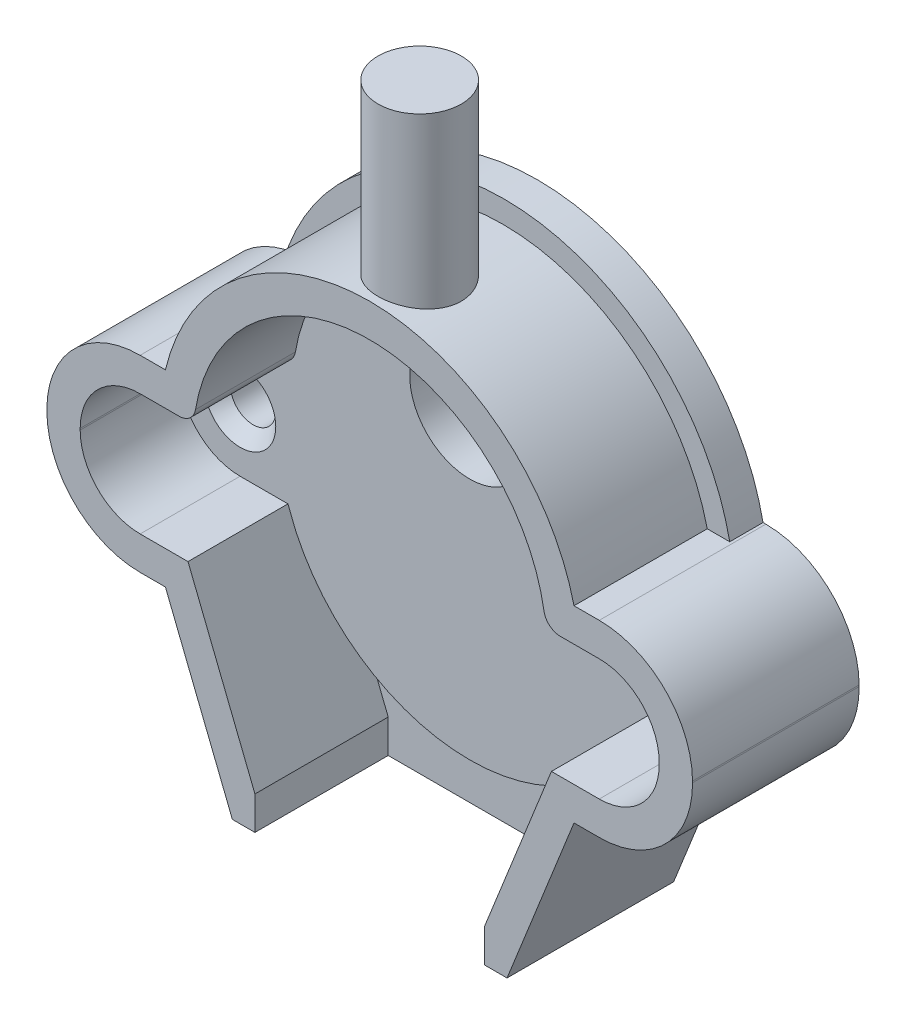
SolidWorks part; units mm, degrees
other "Markup1"
sketch "Sketch20" plane through (-24.612, 32.1867, 12.7) normal (-0.5124, 0.2446, 0.8232) x (0.0203, 0.9618, -0.2731)
other "Markup2"
sketch "Sketch21" plane through (-24.612, 32.1867, 12.7) normal (-0.5124, 0.2446, 0.8232) x (0.0203, 0.9618, -0.2731)
ref_plane "Front Plane" through (0, 0, 0) normal (0, 0, 1) x (1, 0, 0)
ref_plane "Top Plane" through (0, 0, 0) normal (0, 1, 0) x (1, 0, 0)
ref_plane "Right Plane" through (0, 0, 0) normal (1, 0, 0) x (0, 0, -1)
sketch "Sketch1" plane through (0, 0, 0) normal (0, 0, 1) x (1, 0, 0)
  line L0 (10.16, 0) -> (13.9, 0) construction
  line L1 (13.9, 0) -> (10.16, 0) construction
  line L2 (-17.5, 0.0566) -> (-17.5, -0.0566) construction
  line L3 (17.5, 7.1686) -> (15.5744, 7.1686)
  line L4 (17.5, -7.1686) -> (15.5744, -7.1686)
  line L5 (-24.612, 0.0566) -> (-24.612, -0.0566)
  line L6 (24.6118, 0.1131) -> (24.6118, 0)
  line L7 (-15.5744, 7.1686) -> (-17.5, 7.1686)
  line L8 (-15.5744, -7.1686) -> (-17.5, -7.1686)
  line L11 (-10.4702, -19.9603) -> (10.4702, -19.9603)
  line L13 (17.5, 0.0566) -> (17.5, -0.0566) construction
  line L14 (-17.5, 0) -> (17.5, 0) construction
  line L15 (55, 0) -> (-55, 0) construction
  line L16 (-10.4702, -19.9603) -> (-15.5744, -7.1686)
  line L17 (10.4702, -19.9603) -> (15.5744, -7.1686)
  arc A1 (-17.5, -7.1686) -> (-24.612, -0.0566) centre (-17.5, -0.0566) cw
  arc A2 (-17.5, 7.1686) -> (-24.612, 0.0566) centre (-17.5, 0.0566) ccw
  arc A5 (17.5, -7.1686) -> (24.6118, 0) centre (17.5, -0.0566) ccw
  arc A6 (17.5, 7.1686) -> (24.6118, 0.1131) centre (17.5, 0.0566) cw
  arc A9 (15.5744, 7.1686) -> (-15.5744, 7.1686) centre (0, 3.4819) ccw
  point P20 (0, -3.4819)
  point P25 (0, 3.4819)
  point P26 (0, 0)
  point P30 (0, 0)
  dimension "D1" = 1.9256
  dimension "D2" = 0.1131
  dimension "D3" = 35
  dimension "D4" = 7.112
  dimension "D5" = 1.9256
  dimension "D7" = 20.9405
extrude "Boss-Extrude1" add sketch "Sketch1" along normal blind 12.7
sketch "Sketch22" plane through (0, 0, 0) normal (0, 0, -1) x (-1, 0, 0)
  line L0 (-17.2875, 7.1686) -> (17.1369, 7.1686)
  arc A0 (17.1369, 7.1686) -> (-17.2875, 7.1686) centre (-0.0753, 3.628) ccw
shell "Shell1" thickness 2.54 removed face at (0, -1.9647, 12.7)
extrude "Boss-Extrude7" add sketch "Sketch22" against normal blind 2.54
sketch "Sketch7" plane through (0, -17.4203, 0) normal (0, 1, 0) x (1, 0, 0)
  line L1 (-8.749, -12.7) -> (8.749, -12.7)
  line L2 (-8.749, -12.7) -> (-8.749, -2.54)
  line L3 (-8.749, -2.54) -> (8.749, -2.54)
  line L4 (8.749, -12.7) -> (8.749, -2.54)
extrude "Cut-Extrude5" cut sketch "Sketch7" against normal through all
sketch "Sketch13" plane through (0, 0, 2.54) normal (0, 0, 1) x (1, 0, 0)
  line L1 (-17.5, -4.6286) -> (-13.8522, -4.6286)
  line L3 (-16.51, 4.6286) -> (-13.4159, 4.6286)
  line L5 (13.8522, -4.6286) -> (16.51, -4.6286)
  line L6 (13.4159, 4.6286) -> (17.5, 4.6286)
  line L8 (0, 0) -> (0, 8.509) construction
  arc A1 (-16.51, 4.6286) -> (-19.1193, -4.3322) centre (-17.5, 0.0566) ccw
  arc A2 (-19.1193, -4.3322) -> (-17.5, -4.6286) centre (-17.5, -0.0566) ccw
  arc A3 (19.1193, 4.3322) -> (17.5, 4.6286) centre (17.5, 0.0566) ccw
  arc A4 (16.51, -4.6286) -> (19.1193, 4.3322) centre (17.5, -0.0566) ccw
  arc A6 (-13.8522, -4.6286) -> (13.8522, -4.6286) centre (0, 0) ccw
  circle A7 centre (0, 8.509) radius 4.572
  arc A8 (13.4159, 4.6286) -> (-13.4159, 4.6286) centre (0, 3.4819) ccw
  dimension "D2" = 9.144
  dimension "D1" = 8.509
extrude "Boss-Extrude3" add sketch "Sketch13" along normal blind 2.54
sketch "Sketch14" plane through (0, 0, 5.08) normal (0, 0, 1) x (1, 0, 0)
  line L0 (0, 0) -> (0, 8.5) construction
  line L1 (-17.5, 0) -> (17.5, 0) construction
  circle A0 centre (0, 8.5) radius 2.667
  point P6 (0, 0)
  dimension "D1" = 35
  dimension "D2" = 8.5
extrude "Cut-Extrude7" cut sketch "Sketch14" against normal through all both and the other way through all
hole_wizard "#8-32 Tapped Hole1" positions "Sketch16" profile "Sketch17" tap size "#8-32" standard "ANSI Inch" end condition through all
sketch "Sketch16" plane through (0, 0, 5.08) normal (0, 0, 1) x (1, 0, 0)
  point P0 (-17.5, 0)
  point P3 (17.5, 0)
sketch "Sketch17" plane through (-17.5, 0, 5.08) normal (1, 0, 0) x (0, -1, 0)
  line L0 (0, 0) -> (0, 5.08)
  line L1 (0, 5.08) -> (1.7272, 5.08)
  line L2 (1.7272, 5.08) -> (1.7272, 0.9906)
  line L3 (1.7272, 0.9906) -> (2.7178, 0)
  line L5 (2.7178, 0) -> (0, 0)
  line L6 (-1.7272, 0.9906) -> (-2.7178, 0) construction
  line L11 (0, -6.35) -> (0, 107.95) construction
  dimension "Thru Tap Drill Dia." = 3.4544
  dimension "Thru Tap Drill Depth" = 5.08
  dimension "Near C'Sink Dia." = 5.4356
  dimension "Near C'Sink Angle" = 90
cosmetic thread "Hole Thread1" parameters "D2"=4.1656
cosmetic thread "Hole Thread2" parameters "D2"=4.1656
ref_plane "Plane1" through (0, 19.4867, 0) normal (0, 1, 0) x (1, 0, 0)
sketch "Sketch18" plane through (0, 19.4867, 0) normal (0, 1, 0) x (1, 0, 0)
  line L1 (-15.5744, -12.7) -> (15.5744, -12.7) construction
  circle A0 centre (0, -8.89) radius 3.175
  dimension "D2" = 6.35
  dimension "D1" = 3.81
extrude "Boss-Extrude4" add sketch "Sketch18" along normal blind 12.7 and the other way blind 1.27
sketch "Sketch19" plane through (0, 0, 0) normal (0, 0, -1) x (-1, 0, 0)
  circle A0 centre (0, 8.5) radius 3.937
  dimension "D1" = 7.874
extrude "Cut-Extrude8" cut sketch "Sketch19" against normal blind 2.54
fillet "Fillet1" radius 1.27 2 edges at (-13.4159, 4.6286, 8.89) (13.4159, 4.6286, 8.89)
